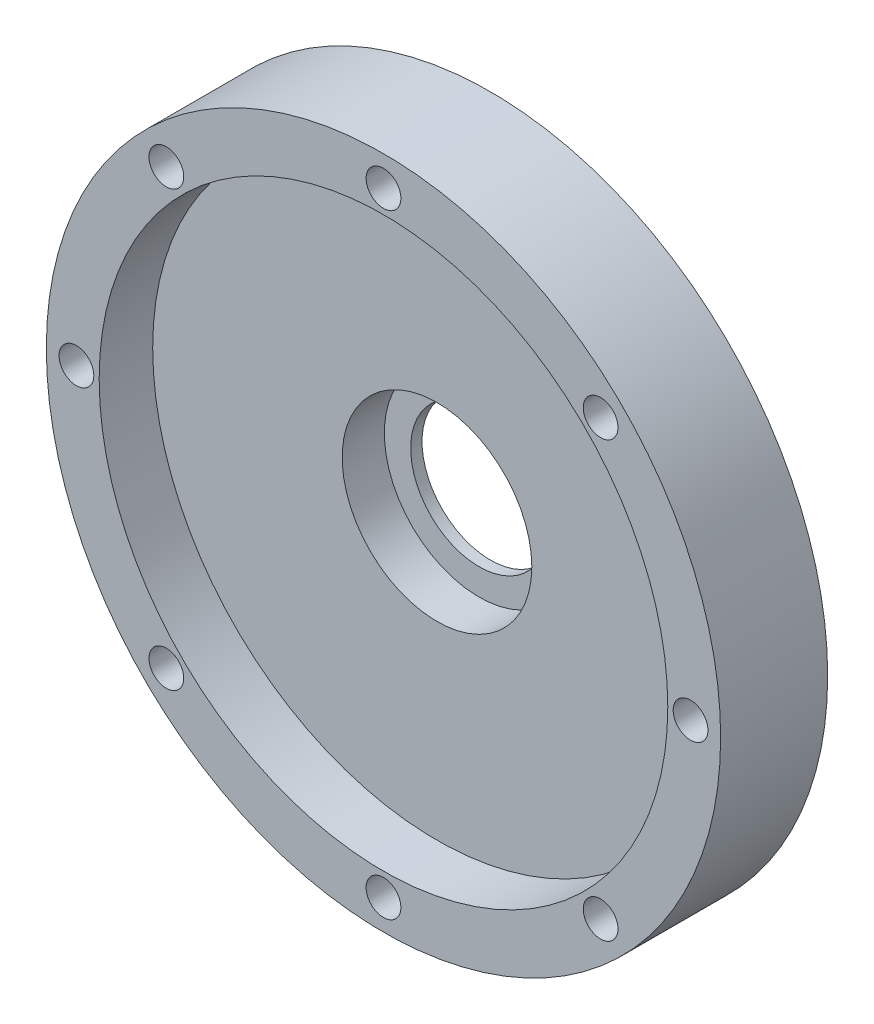
SolidWorks part; units mm, degrees
material "ABS"
ref_plane "Front Plane" through (0, 0, 0) normal (0, 0, 1) x (1, 0, 0)
ref_plane "Top Plane" through (0, 0, 0) normal (0, 1, 0) x (1, 0, 0)
ref_plane "Right Plane" through (0, 0, 0) normal (1, 0, 0) x (0, 0, -1)
sketch "Sketch1" plane through (0, 0, 0) normal (0, 0, 1) x (1, 0, 0)
  circle A0 centre (0, 0) radius 32.004
  dimension "D1" = 64.008
extrude "Boss-Extrude1" add sketch "Sketch1" along normal blind 10.16
sketch "Sketch2" plane through (0, 0, 10.16) normal (0, 0, 1) x (1, 0, 0)
  circle A0 centre (0, 0) radius 26.9875
  dimension "D1" = 53.975
extrude "Cut-Extrude1" cut sketch "Sketch2" against normal blind 5.08
sketch "Sketch3" plane through (0, 0, 5.08) normal (0, 0, 1) x (1, 0, 0)
  circle A0 centre (0, 0) radius 9
  dimension "D1" = 18
extrude "Cut-Extrude2" cut sketch "Sketch3" against normal blind 4
sketch "Sketch4" plane through (0, 0, 1.08) normal (0, 0, 1) x (1, 0, 0)
  circle A0 centre (0, 0) radius 6.5
  dimension "D1" = 13
extrude "Cut-Extrude3" cut sketch "Sketch4" against normal through all
sketch "Sketch5" plane through (0, 0, 10.16) normal (0, 0, 1) x (1, 0, 0)
  line L0 (0, 0) -> (0, 32.004) construction
  line L2 (0, 0) -> (22.6302, 22.6302) construction
  line L3 (0, 0) -> (32.004, 0) construction
  line L4 (0, 0) -> (22.6302, -22.6302) construction
  line L5 (0, 0) -> (0, -32.004) construction
  line L6 (0, 0) -> (-22.6302, -22.6302) construction
  line L7 (0, 0) -> (-32.004, 0) construction
  line L8 (0, 0) -> (-22.6302, 22.6302) construction
  line L9 (0, 0) -> (0, 29.1465) construction
  circle A0 centre (0, 0) radius 32.004 construction
  point P6 (0, 29.1465)
  point P15 (20.6097, 20.6097)
  point P17 (29.1465, 0)
  point P19 (20.6097, -20.6097)
  point P21 (0, -29.1465)
  point P23 (-20.6097, -20.6097)
  point P25 (-29.1465, 0)
  point P27 (-20.6097, 20.6097)
  dimension "D1" = 29.1465
  dimension "D2" = 8
hole_wizard "M4x0.7 Tapped Hole1" positions "Sketch5" profile "Sketch6" tap size "M4x0.7" standard "ANSI Metric" end condition through all
sketch "Sketch6" plane through (-20.6097, 20.6097, 10.16) normal (1, 0, 0) x (0, -1, 0)
  line L0 (0, 0) -> (0, 10.16)
  line L1 (0, 10.16) -> (1.65, 10.16)
  line L2 (1.65, 10.16) -> (1.65, 0)
  line L5 (1.65, 0) -> (0, 0)
  line L11 (0, -6.35) -> (0, 107.95) construction
  dimension "Thru Tap Drill Dia." = 3.3
  dimension "Thru Tap Drill Depth" = 10.16
cosmetic thread "Hole Thread1" parameters "D2"=4
cosmetic thread "Hole Thread2" parameters "D2"=4
cosmetic thread "Hole Thread3" parameters "D2"=4
cosmetic thread "Hole Thread4" parameters "D2"=4
cosmetic thread "Hole Thread5" parameters "D2"=4
cosmetic thread "Hole Thread6" parameters "D2"=4
cosmetic thread "Hole Thread7" parameters "D2"=4
cosmetic thread "Hole Thread8" parameters "D2"=4
